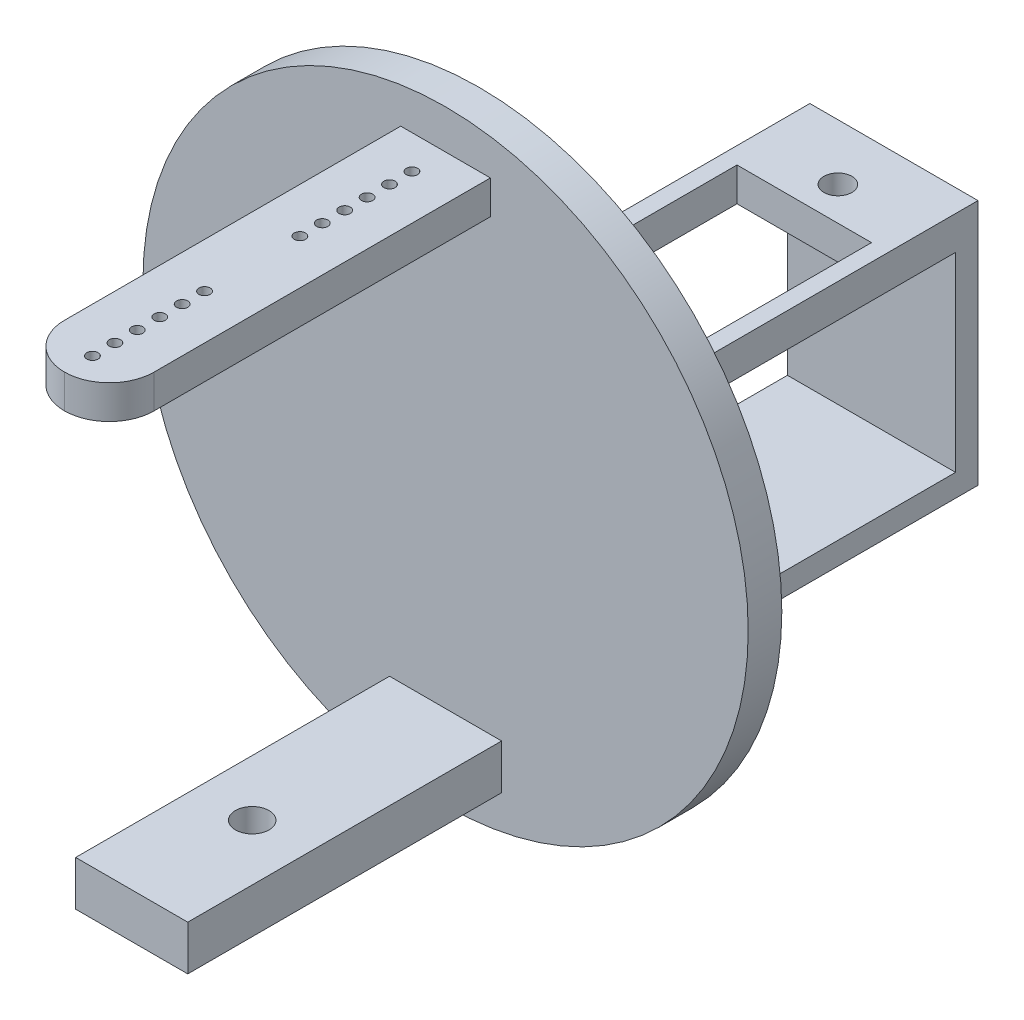
SolidWorks part; units mm, degrees
ref_plane "Front Plane" through (0, 0, 0) normal (0, 0, 1) x (1, 0, 0)
ref_plane "Top Plane" through (0, 0, 0) normal (0, 1, 0) x (1, 0, 0)
ref_plane "Right Plane" through (0, 0, 0) normal (1, 0, 0) x (0, 0, -1)
sketch "Sketch1" plane through (0, 0, 0) normal (0, 0, 1) x (1, 0, 0)
  circle A0 centre (0, 0) radius 27
  dimension "D1" = 54
extrude "Boss-Extrude1" add sketch "Sketch1" along normal blind 3
sketch "Sketch2" plane through (0, 0, 3) normal (0, 0, 1) x (1, 0, 0)
  line L1 (-4, 23.5) -> (4, 23.5)
  line L2 (-4, 23.5) -> (-4, 20.5)
  line L3 (-4, 20.5) -> (4, 20.5)
  line L4 (4, 23.5) -> (4, 20.5)
  line L5 (-4, 23.5) -> (4, 20.5) construction
  line L6 (-4, 20.5) -> (4, 23.5) construction
  point P0 (0, 22)
  dimension "D1" = 23.5
  dimension "D2" = 8
  dimension "D3" = 3
extrude "Boss-Extrude2" add sketch "Sketch2" along normal blind 34
sketch "Sketch5" plane through (0, 23.5, 0) normal (0, 1, 0) x (1, 0, 0)
  line L0 (4, -3) -> (-4, -3) construction
  circle A0 centre (0, -6) radius 0.5
  circle A1 centre (0, -8) radius 0.5
  circle A2 centre (0, -10) radius 0.5
  circle A3 centre (0, -12) radius 0.5
  circle A4 centre (0, -14) radius 0.5
  circle A5 centre (0, -16) radius 0.5
  circle A6 centre (0, -34.5) radius 0.5
  circle A7 centre (0, -32.5) radius 0.5
  circle A8 centre (0, -30.5) radius 0.5
  circle A9 centre (0, -28.5) radius 0.5
  circle A10 centre (0, -26.5) radius 0.5
  circle A11 centre (0, -24.5) radius 0.5
  dimension "D1" = 1
  dimension "D4" = 2
  dimension "D6" = 8.5
  dimension "D7" = 2
  dimension "D2" = 3
  dimension "D3" = 6
  dimension "D5" = 6
extrude "Cut-Extrude1" cut sketch "Sketch5" against normal blind 5
fillet "Fillet1" radius 4 2 edges at (-4, 22, 37) (4, 22, 37)
sketch "Sketch6" plane through (0, 0, 0) normal (0, 0, -1) x (-1, 0, 0)
  line L1 (-7.5, 3.5) -> (7.5, 3.5)
  line L2 (-7.5, 3.5) -> (-7.5, 0.5)
  line L3 (-7.5, 0.5) -> (7.5, 0.5)
  line L4 (7.5, 3.5) -> (7.5, 0.5)
  line L5 (-7.5, 3.5) -> (7.5, 0.5) construction
  line L6 (-7.5, 0.5) -> (7.5, 3.5) construction
  point P0 (0, 2)
  point P6 (0, 0)
  dimension "D1" = 3
  dimension "D2" = 15
  dimension "D3" = 2
extrude "Boss-Extrude3" add sketch "Sketch6" along normal blind 35
sketch "Sketch7" plane through (0, 3.5, 0) normal (0, 1, 0) x (1, 0, 0)
  line L0 (-7.5, 35) -> (-7.5, 0) construction
  line L1 (-6, 29) -> (6, 29)
  line L2 (-6, 29) -> (-6, 6)
  line L3 (-6, 6) -> (6, 6)
  line L4 (6, 29) -> (6, 6)
  line L5 (-6, 29) -> (6, 6) construction
  line L6 (-6, 6) -> (6, 29) construction
  line L7 (0, 32) -> (0, 3) construction
  circle A0 centre (0, 32) radius 1.25
  circle A1 centre (0, 3) radius 1.25
  point P0 (0, 17.5)
  point P10 (-7.5, 17.5)
  point P13 (0, 17.5)
  dimension "D3" = 2.5
  dimension "D1" = 12
  dimension "D2" = 23
  dimension "D4" = 29
extrude "Cut-Extrude2" cut sketch "Sketch7" against normal blind 5
sketch "Sketch8" plane through (0, 0, -35) normal (0, 0, -1) x (-1, 0, 0)
  line L0 (7.5, 0.5) -> (7.5, 3.5) construction
  line L1 (-7.5, 3.5) -> (7.5, 3.5)
  line L2 (-7.5, 3.5) -> (-7.5, -16.5)
  line L3 (-7.5, -16.5) -> (7.5, -16.5)
  line L4 (7.5, 3.5) -> (7.5, -16.5)
  line L5 (7.5, 3.5) -> (-7.5, 3.5) construction
  point P5 (7.5, 3.5)
  dimension "D1" = 20
extrude "Boss-Extrude4" add sketch "Sketch8" along normal blind 2
sketch "Sketch9" plane through (0, -16.5, 0) normal (0, -1, 0) x (1, 0, 0)
  line L1 (7.5, -37) -> (-7.5, -37)
  line L2 (7.5, -37) -> (7.5, 0)
  line L3 (7.5, 0) -> (-7.5, 0)
  line L4 (-7.5, -37) -> (-7.5, 0)
extrude "Boss-Extrude5" add sketch "Sketch9" along normal blind 2
sketch "Sketch10" plane through (0, 0, 3) normal (0, 0, 1) x (1, 0, 0)
  line L0 (-4, 20.5) -> (0, 20.5) construction
  line L1 (-5, -19.5) -> (5, -19.5)
  line L2 (-5, -19.5) -> (-5, -23.5)
  line L3 (-5, -23.5) -> (5, -23.5)
  line L4 (5, -19.5) -> (5, -23.5)
  line L5 (-5, -19.5) -> (5, -23.5) construction
  line L6 (-5, -23.5) -> (5, -19.5) construction
  point P0 (0, -21.5)
  point P5 (0, -19.5)
  dimension "D1" = 4
  dimension "D2" = 10
  dimension "D3" = 40
extrude "Boss-Extrude6" add sketch "Sketch10" along normal blind 28
sketch "Sketch11" plane through (0, -19.5, 0) normal (0, 1, 0) x (1, 0, 0)
  line L0 (-5, -3) -> (5, -3) construction
  circle A0 centre (0, -20.25) radius 1.5
  point P4 (0, 0)
  dimension "D1" = 3
  dimension "D2" = 17.25
extrude "Cut-Extrude3" cut sketch "Sketch11" against normal blind 5
sketch "Sketch12" plane through (0, -18.5, 0) normal (0, -1, 0) x (1, 0, 0)
  line L0 (7.5, 0) -> (-7.5, 0) construction
  circle A0 centre (0, -22.5) radius 1.5
  point P2 (0, 0)
  dimension "D1" = 3
  dimension "D2" = 22.5
extrude "Boss-Extrude7" add sketch "Sketch12" along normal blind 5
